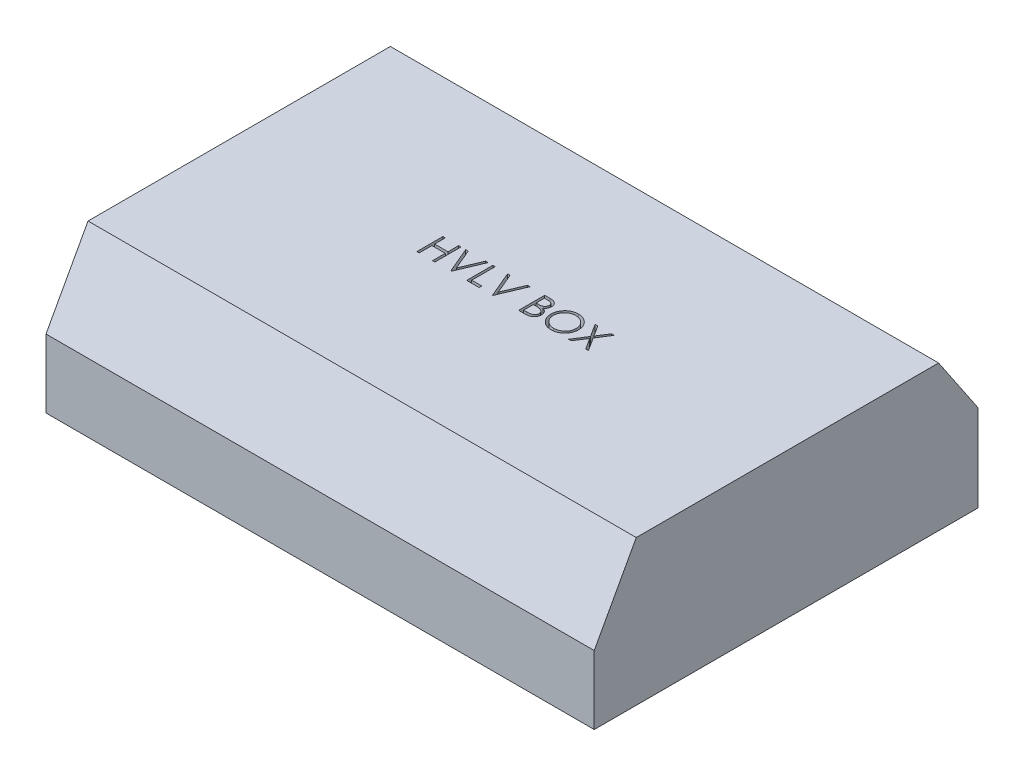
SolidWorks part; units mm, degrees
ref_plane "정면" through (0, 0, 0) normal (0, 0, 1) x (1, 0, 0)
ref_plane "윗면" through (0, 0, 0) normal (0, 1, 0) x (1, 0, 0)
ref_plane "우측면" through (0, 0, 0) normal (1, 0, 0) x (0, 0, -1)
sketch "Sketch1" plane through (0, 0, 0) normal (0, 1, 0) x (1, 0, 0)
  line L1 (-200, -140) -> (200, -140)
  line L2 (-200, -140) -> (-200, 140)
  line L3 (-200, 140) -> (200, 140)
  line L4 (200, -140) -> (200, 140)
  line L5 (-200, -140) -> (200, 140) construction
  line L6 (-200, 140) -> (200, -140) construction
  point P0 (0, 0)
  dimension "D1" = 280
  dimension "D2" = 400
extrude "Boss-Extrude1" add sketch "Sketch1" along normal blind 53 and the other way blind 53
sketch "Sketch2" plane through (0, 53, 0) normal (0, 1, 0) x (1, 0, 0)
  text T0 "HVLV BOX" font "Century Gothic" height in points 72
extrude "Cut-Extrude1" cut sketch "Sketch2" against normal blind 53
sketch "Sketch3" plane through (-200, 0, 0) normal (-1, 0, 0) x (0, 0, 1)
  line L0 (-140, 10.3704) -> (-111.2574, 53)
  line L1 (-140, -53) -> (-140, 53) construction
  line L2 (-140, 53) -> (140, 53) construction
  line L3 (-111.2574, 53) -> (-140, 53)
  line L4 (-140, 53) -> (-140, 10.3704)
  line L5 (109.337, 53) -> (140, 53)
  line L6 (140, 53) -> (140, -3.0727)
  line L7 (140, -53) -> (140, 53) construction
  line L8 (140, -3.0727) -> (109.337, 53)
  point P14 (109.337, 53)
  point P15 (140, 14.3393)
  point P16 (140, 7.1696)
  point P17 (140, -3.0727)
extrude "Cut-Extrude2" cut sketch "Sketch3" against normal through all
